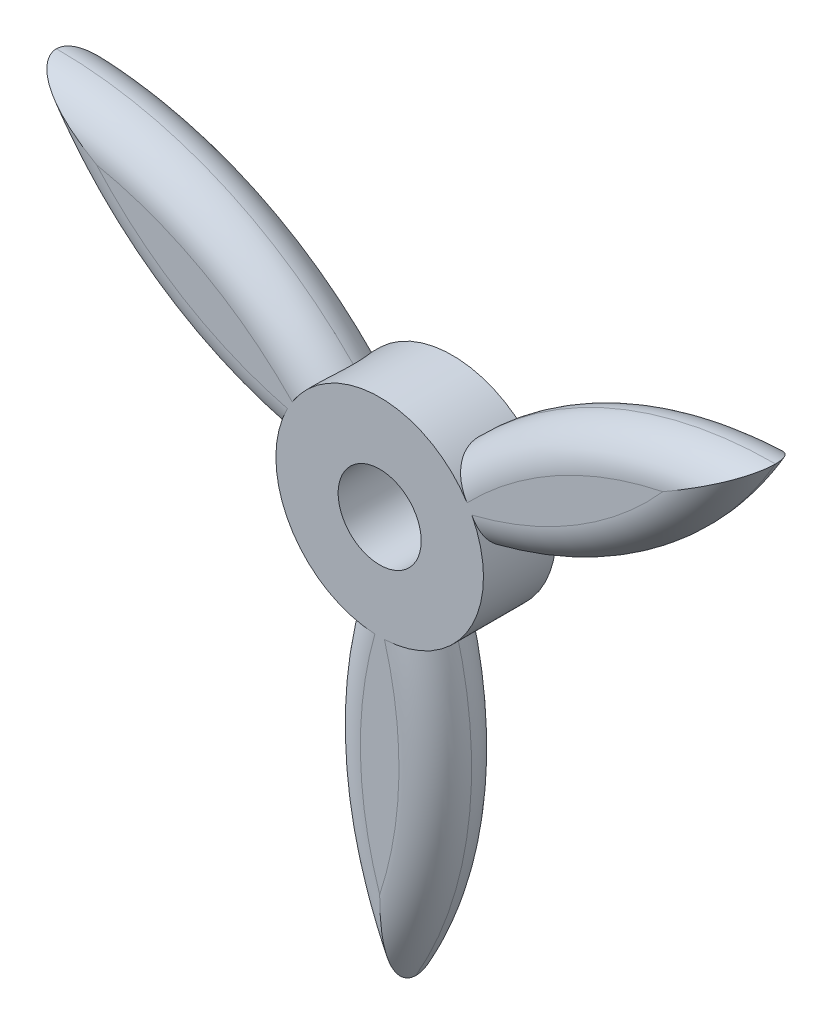
SolidWorks part; units mm, degrees
ref_plane "Front Plane" through (0, 0, 0) normal (0, 0, 1) x (1, 0, 0)
ref_plane "Top Plane" through (0, 0, 0) normal (0, 1, 0) x (1, 0, 0)
ref_plane "Right Plane" through (0, 0, 0) normal (1, 0, 0) x (0, 0, -1)
sketch "Sketch1" plane through (0, 0, 0) normal (0, 0, 1) x (1, 0, 0)
  arc A21 (-9.9216, 1.25) -> (-3.8783, -9.2173) centre (0, 0) ccw
  circle A22 centre (0, 0) radius 4
  arc A24 (34.641, 20) -> (6.0433, 7.9673) centre (34.641, -20) ccw
  arc A30 (-34.641, 20) -> (-9.9216, 1.25) centre (0, 40) ccw
  arc A32 (0, -40) -> (3.8783, -9.2173) centre (-34.641, -20) ccw
  arc A33 (3.8783, -9.2173) -> (9.9216, 1.25) centre (0, 0) ccw
  arc A35 (9.9216, 1.25) -> (34.641, 20) centre (0, 40) ccw
  arc A36 (6.0433, 7.9673) -> (-6.0433, 7.9673) centre (0, 0) ccw
  arc A37 (-6.0433, 7.9673) -> (-34.641, 20) centre (-34.641, -20) ccw
  arc A39 (-3.8783, -9.2173) -> (0, -40) centre (34.641, -20) ccw
extrude "Boss-Extrude1" add sketch "Sketch1" along normal blind 7
fillet "Fillet2" radius 3.5 12 edges at (-19.128, 16.8693, 0) (-24.1733, 8.1307, 0) (19.128, 16.8693, 0) (24.1733, 8.1307, 0) (5.0453, -25, 0) (-5.0453, -25, 0) (-5.0453, -25, 7) (5.0453, -25, 7) (24.1733, 8.1307, 7) (19.128, 16.8693, 7) (-19.128, 16.8693, 7) (-24.1733, 8.1307, 7)
